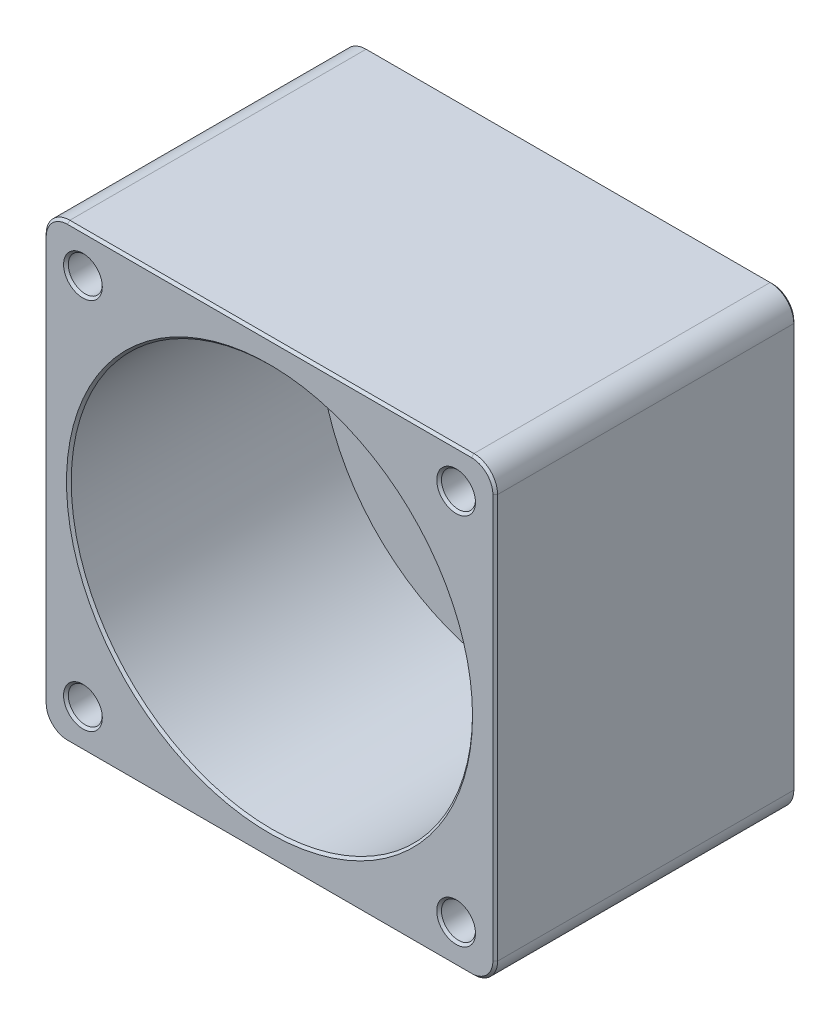
SolidWorks part; units mm, degrees
material "6061-T6 (SS)"
ref_plane "Front Plane" through (0, 0, 0) normal (0, 0, 1) x (1, 0, 0)
ref_plane "Top Plane" through (0, 0, 0) normal (0, 1, 0) x (1, 0, 0)
ref_plane "Right Plane" through (0, 0, 0) normal (1, 0, 0) x (0, 0, -1)
sketch "Sketch1" plane through (0, 0, 0) normal (0, 0, 1) x (1, 0, 0)
  line L1 (23.622, 23.622) -> (-23.622, 23.622) construction
  line L2 (23.622, 23.622) -> (23.622, -23.622) construction
  line L3 (23.622, -23.622) -> (-23.622, -23.622) construction
  line L4 (-23.622, 23.622) -> (-23.622, -23.622) construction
  line L5 (0, -23.622) -> (0, 23.622) construction
  line L6 (23.622, 0) -> (-23.622, 0) construction
  line L7 (28.575, 28.575) -> (-28.575, 28.575)
  line L8 (28.575, 28.575) -> (28.575, -28.575)
  line L9 (28.575, -28.575) -> (-28.575, -28.575)
  line L10 (-28.575, 28.575) -> (-28.575, -28.575)
  line L11 (28.575, 28.575) -> (-28.575, -28.575) construction
  line L12 (28.575, -28.575) -> (-28.575, 28.575) construction
  circle A0 centre (0, 0) radius 3.9992
  circle A1 centre (-23.622, 23.622) radius 2.1526
  circle A2 centre (23.622, 23.622) radius 2.1526
  circle A3 centre (23.622, -23.622) radius 2.1526
  circle A4 centre (-23.622, -23.622) radius 2.1526
  circle A5 centre (0, 0) radius 25.4
  point P0 (0, 0)
  point P4 (0, 0)
  dimension "D3" = 7.9985
  dimension "D4" = 4.3053
  dimension "D5" = 50.8
  dimension "D1" = 47.244
  dimension "D2" = 57.15
extrude "Boss-Extrude1" add sketch "Sketch1" along normal blind 6.35 contours A5 A0 | L7 L10 L9 L8 A5 A4 A3 A2 A1 region at (27.7668, 0, 0) region at (-24.6816, 0, 0)
extrude "Boss-Extrude2" add sketch "Sketch1<3>" along normal blind 38.1 contours L7 L10 L9 L8 A5 A4 A3 A2 A1 region at (27.7668, 0, 0)
sketch "Sketch1<3>" plane through (0, 0, 0) normal (0, 0, 1) x (1, 0, 0) same geometry as "Sketch1"
fillet "Fillet1" radius 3 4 edges at (-28.575, 28.575, 19.05) (28.575, 28.575, 19.05) (28.575, -28.575, 19.05) (-28.575, -28.575, 19.05)
chamfer "Chamfer1" distance 0.3 angle 45 27 edges at (-21.4694, -23.622, 0) (25.7747, -23.622, 0) (25.7747, 23.622, 0) (-21.4694, 23.622, 0) (-27.6963, -27.6963, 0) (0, -28.575, 0) (27.6963, -27.6963, 0) (28.575, 0, 0) (27.6963, 27.6963, 0) (0, 28.575, 0) (-27.6963, 27.6963, 0) (-28.575, 0, 0) (3.9992, 0, 0) (27.6963, 27.6963, 38.1) (28.575, 0, 38.1) (27.6963, -27.6963, 38.1) (0, -28.575, 38.1) (-27.6963, -27.6963, 38.1) (-28.575, 0, 38.1) (-27.6963, 27.6963, 38.1) (0, 28.575, 38.1) (-21.4694, 23.622, 38.1) (25.7747, 23.622, 38.1) (25.7747, -23.622, 38.1) (-21.4694, -23.622, 38.1) (25.4, 0, 38.1) (3.9992, 0, 6.35)
